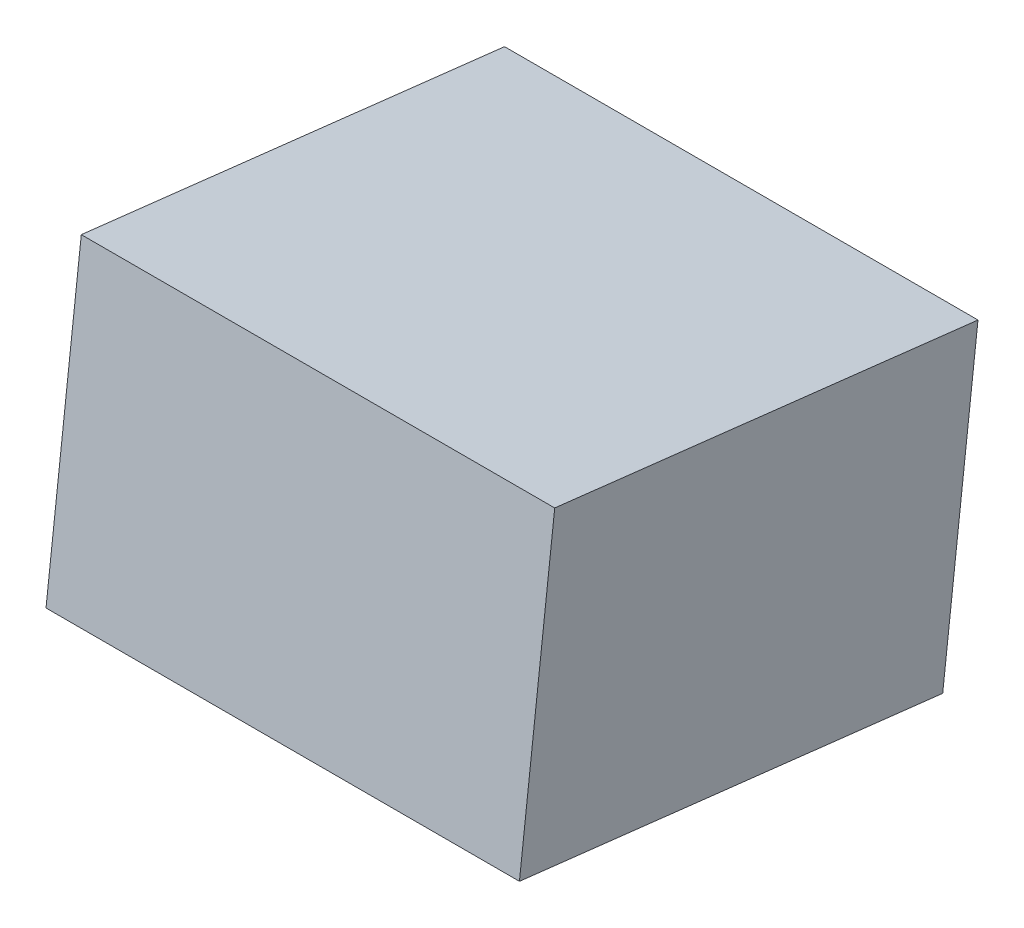
SolidWorks part; units mm, degrees
ref_plane "Front Plane" through (0, 0, 0) normal (0, 0, 1) x (1, 0, 0)
ref_plane "Top Plane" through (0, 0, 0) normal (0, 1, 0) x (1, 0, 0)
ref_plane "Right Plane" through (0, 0, 0) normal (1, 0, 0) x (0, 0, -1)
sketch "Sketch1" plane through (0, 358.8799, -41.4225) normal (0, 0.9934, -0.1147) x (1, 0, 0)
  line L1 (-231.6731, 126.7254) -> (-31.6731, 126.7254)
  line L2 (-231.6731, 126.7254) -> (-231.6731, 306.7254)
  line L3 (-231.6731, 306.7254) -> (-31.6731, 306.7254)
  line L4 (-31.6731, 126.7254) -> (-31.6731, 306.7254)
  line L5 (-231.6731, 126.7254) -> (-31.6731, 306.7254) construction
  line L6 (-231.6731, 306.7254) -> (-31.6731, 126.7254) construction
  point P0 (-131.6731, 216.7254)
  dimension "D1" = 180
  dimension "D2" = 200
extrude "Boss-Extrude1" add sketch "Sketch1" along normal blind 130
